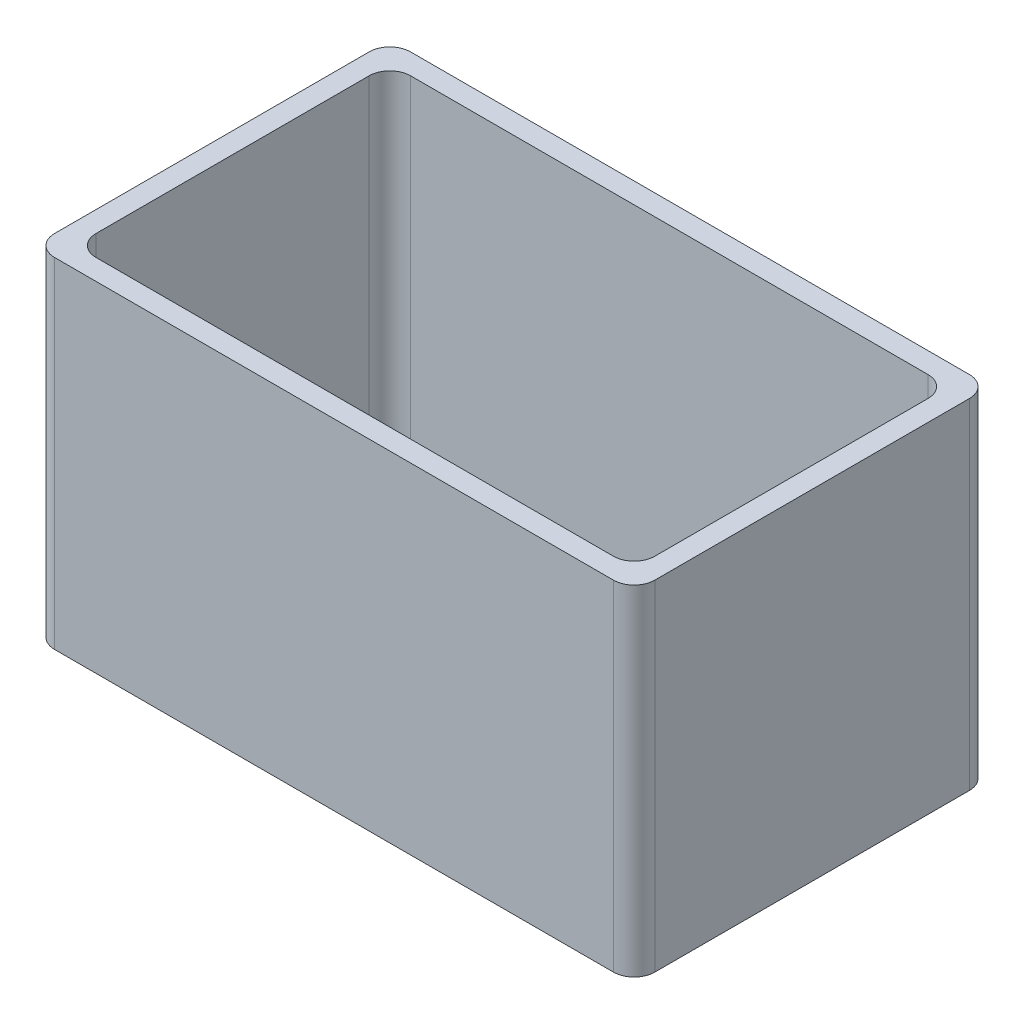
SolidWorks part; units mm, degrees
ref_plane "Alzado" through (0, 0, 0) normal (0, 0, 1) x (1, 0, 0)
ref_plane "Planta" through (0, 0, 0) normal (0, 1, 0) x (1, 0, 0)
ref_plane "Vista lateral" through (0, 0, 0) normal (1, 0, 0) x (0, 0, -1)
sketch "Croquis1" plane through (0, 0, 0) normal (0, 0, 1) x (1, 0, 0)
  line L1 (-145, -82) -> (145, -82)
  line L2 (-145, -82) -> (-145, 82)
  line L3 (-145, 82) -> (145, 82)
  line L4 (145, -82) -> (145, 82)
  line L5 (-145, -82) -> (145, 82) construction
  line L6 (-145, 82) -> (145, -82) construction
  point P0 (0, 0)
  dimension "D1" = 290
  dimension "D2" = 164
extrude "Saliente-Extruir1" add sketch "Croquis1" along normal blind 172
fillet "Redondeo1" radius 10 4 edges at (-145, 0, 0) (145, 0, 0) (145, 0, 172) (-145, 0, 172)
shell "Vaciado1" thickness 10 removed face at (0, 82, 86)
sketch "Croquis2" plane through (0, 82, 0) normal (0, 1, 0) x (1, 0, 0)
  line L0 (-134.7401, -6.2756) -> (134.1789, -6.2756) construction
  text T0 "SOLIDWORKS 2026 "
fillet "Redondeo2" radius 10 4 edges at (135, 5, 10) (135, 5, 162) (-135, 5, 162) (-135, 5, 10)
